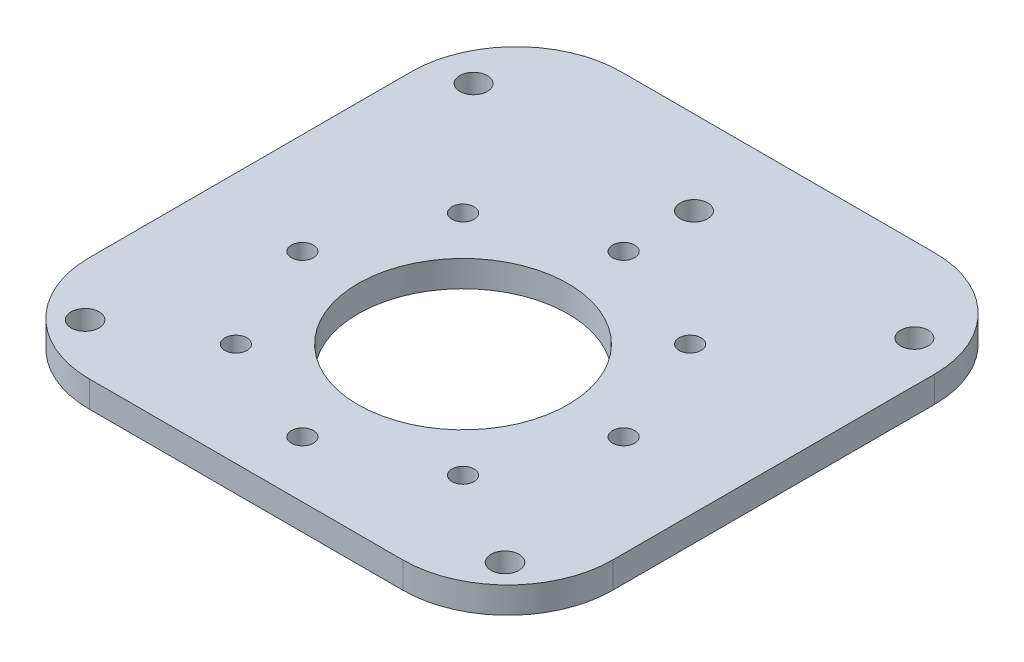
SolidWorks part; units mm, degrees
material "6061 Alloy"
ref_plane "Front Plane" through (0, 0, 0) normal (0, 0, 1) x (1, 0, 0)
ref_plane "Top Plane" through (0, 0, 0) normal (0, 1, 0) x (1, 0, 0)
ref_plane "Right Plane" through (0, 0, 0) normal (1, 0, 0) x (0, 0, -1)
sketch "Sketch2" plane through (0, 0, 0) normal (0, 1, 0) x (1, 0, 0)
  line L0 (0, 0) -> (0, 35.56) construction
  line L1 (-47.5, -60.96) -> (-47.5, 35.56)
  line L2 (47.5, -60.96) -> (47.5, 35.56)
  line L3 (-47.5, 35.56) -> (47.5, 35.56)
  line L4 (-47.5, -60.96) -> (47.5, -60.96)
  point P3 (47.5, -12.7)
  point P5 (0, 35.56)
  point P12 (0, -60.96)
  dimension "D1" = 96.52
  dimension "D2" = 95
  dimension "D3" = 12.7
extrude "Boss-Extrude3" add sketch "Sketch2" along normal blind 4.7625
sketch "Sketch3" plane through (0, 4.7625, 0) normal (0, 1, 0) x (1, 0, 0)
  line L0 (47.5, 35.56) -> (-47.5, 35.56) construction
  circle A1 centre (0, -21.59) radius 19.05
  dimension "D2" = 38.1
  dimension "D3" = 57.15
extrude "Cut-Extrude1" cut sketch "Sketch3" against normal through all
sketch "Sketch4" plane through (0, 4.7625, 0) normal (0, 1, 0) x (1, 0, 0)
  line L0 (47.5, 35.56) -> (-47.5, 35.56) construction
  line L1 (0, 35.56) -> (0, 55.3884) construction
  point P0 (-40, 20.32)
  point P7 (40, 20.32)
  point P8 (0, 20.32)
  point P10 (0, 20.32)
  dimension "D1" = 15.24
  dimension "D2" = 80
hole_wizard "M6x1.0 Tapped Hole1" positions "Sketch4" profile "Sketch6" tap size "M6x1.0" standard "ANSI Metric"
sketch "Sketch6" plane through (-40, 4.7625, -20.32) normal (1, 0, 0) x (0, 0, 1)
  line L0 (0, 0) -> (0, 6.2647)
  line L1 (0, 6.2647) -> (2.5, 4.7625)
  line L2 (2.5, 4.7625) -> (2.5, 0)
  line L5 (2.5, 0) -> (0, 0)
  line L10 (0, 6.2647) -> (-2.5, 4.7625) construction
  line L11 (0, -6.35) -> (0, 107.95) construction
  dimension "Tap Drill Dia." = 5
  dimension "Tap Drill Depth" = 4.7625
  dimension "Drill Angle" = 118
sketch "Sketch7" plane through (0, 4.7625, 0) normal (0, 1, 0) x (1, 0, 0)
  line L0 (0, 0) -> (0, -60.96) construction
  line L1 (-47.5, -60.96) -> (47.5, -60.96) construction
  circle A2 centre (-38.1, -52.07) radius 2.54
  circle A3 centre (38.1, -52.07) radius 2.54
  dimension "D4" = 5.08
  dimension "D6" = 38.1
  dimension "D1" = 52.07
extrude "Cut-Extrude2" cut sketch "Sketch7" against normal blind 7.62
sketch "Sketch12" plane through (0, 4.7625, 0) normal (0, 1, 0) x (1, 0, 0)
  line L0 (47.5, 35.56) -> (-47.5, 35.56) construction
  circle A0 centre (0, -21.59) radius 29.1465
  circle A1 centre (0, 7.5565) radius 2
  circle A2 centre (20.6097, -0.9803) radius 2
  circle A3 centre (29.1465, -21.59) radius 2
  circle A4 centre (20.6097, -42.1997) radius 2
  circle A5 centre (0, -50.7365) radius 2
  circle A6 centre (-20.6097, -42.1997) radius 2
  circle A7 centre (-29.1465, -21.59) radius 2
  circle A8 centre (-20.6097, -0.9803) radius 2
  point P25 (0, -21.59)
  dimension "D1" = 4
  dimension "D2" = 58.293
  dimension "D3" = 57.15
  dimension "D4" = 8
extrude "Cut-Extrude3" cut sketch "Sketch12" against normal through all contours A8 | A7 | A6 | A5 | A4 | A3 | A2 | A1
fillet "Fillet1" radius 19.05 4 edges at (47.5, 2.3813, -35.56) (47.5, 2.3813, 60.96) (-47.5, 2.3813, 60.96) (-47.5, 2.3813, -35.56)
